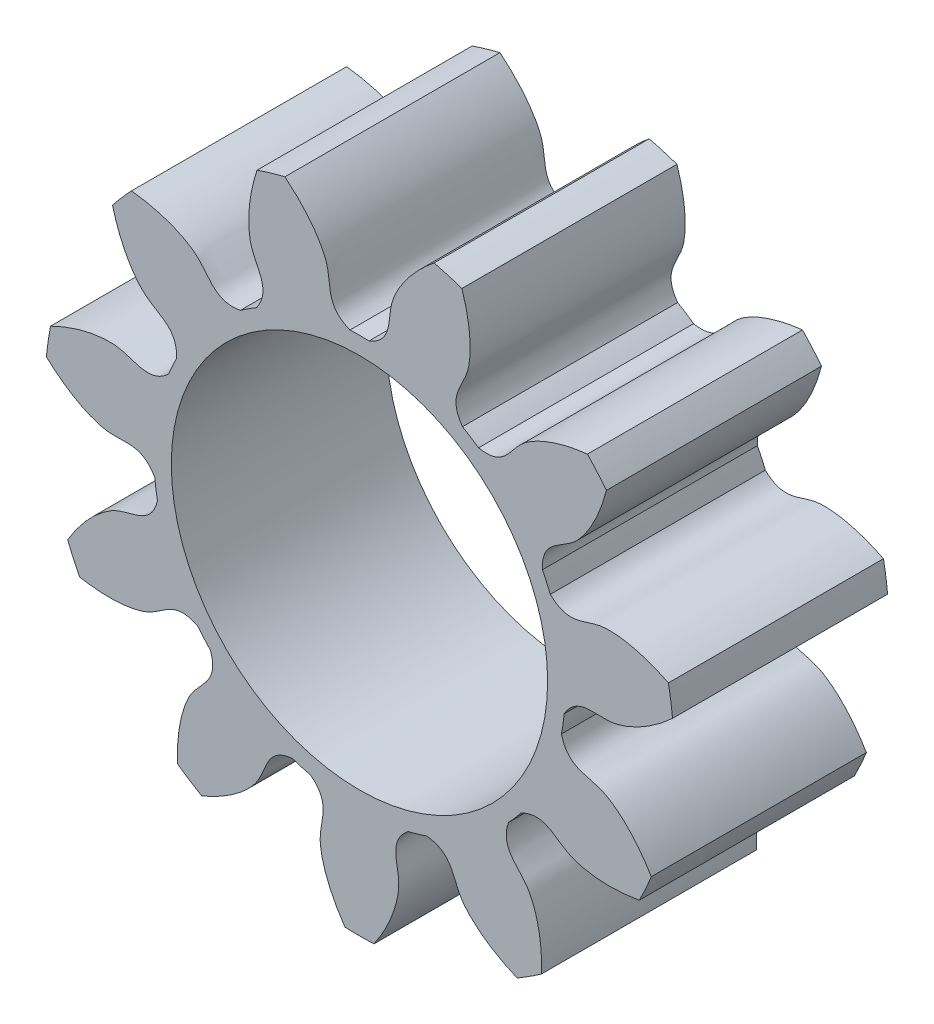
SolidWorks part; units mm, degrees
ref_plane "前视基准面" through (0, 0, 0) normal (0, 0, 1) x (1, 0, 0)
ref_plane "上视基准面" through (0, 0, 0) normal (0, 1, 0) x (1, 0, 0)
ref_plane "右视基准面" through (0, 0, 0) normal (1, 0, 0) x (0, 0, -1)
other "Configuration Table"
sketch "草图1" plane through (0, 0, 0) normal (0, 0, 1) x (1, 0, 0)
  circle A0 centre (0, 0) radius 2.925
extrude "凸台-拉伸1" add sketch "草图1" along normal blind 2
ref_axis "基准轴1" through (0, 0, 2) along (0, 0, -1)
sketch "草图2" plane through (0, 0, 0) normal (0, 0, 1) x (1, 0, 0)
  line L0 (0, 0) -> (0, 2.925) construction
  circle A0 centre (0, 0) radius 2.925 construction
  arc A1 (0.0885, 1.9104) -> (-0.0885, 1.9104) centre (0, 0) ccw
  arc A2 (1.6426, 3.2805) -> (-1.6426, 3.2805) centre (0, 0) ccw
  spline S0 degree 3 poles (0.0885, 1.9104) (0.3157, 2.001) (0.2586, 2.1861) (0.3071, 2.3434) (0.3099, 2.3518) (0.3131, 2.361) (0.3169, 2.371) (0.3212, 2.3818) (0.326, 2.3934) (0.3315, 2.4057) (0.3376, 2.4188) (0.3444, 2.4325) (0.3519, 2.447) (0.3602, 2.4621) (0.3692, 2.4779) (0.3789, 2.4942) (0.3895, 2.5112) (0.401, 2.5287) (0.4133, 2.5468) (0.4265, 2.5654) (0.4407, 2.5844) (0.4558, 2.6039) (0.4718, 2.6238) (0.4889, 2.6441) (0.5069, 2.6648) (0.526, 2.6858) (0.5462, 2.707) (0.5674, 2.7286) (0.5898, 2.7503) (0.6132, 2.7722) (0.6378, 2.7943) (0.6635, 2.8165) (0.6903, 2.8388) (0.7183, 2.8611) (0.7475, 2.8834) (0.7779, 2.9057) (0.8095, 2.9279) (0.8423, 2.9499) (0.8764, 2.9718) (0.9116, 2.9936) (0.9481, 3.015) (0.9858, 3.0363) (1.0247, 3.0571) (1.0649, 3.0777) (1.1063, 3.0978) (1.149, 3.1175) (1.1929, 3.1367) (1.238, 3.1554) (1.2844, 3.1735) (1.332, 3.191) (1.3808, 3.2078) (1.4308, 3.224) (1.482, 3.2394) (1.5525, 3.2591) (1.6063, 3.2723) (1.6426, 3.2805) knots 0 0 0 0 0.219011 0.222642 0.226699 0.231184 0.236096 0.241435 0.247201 0.253394 0.260015 0.267062 0.274537 0.282438 0.290767 0.299523 0.308706 0.318316 0.328354 0.338818 0.34971 0.361028 0.372774 0.384947 0.397547 0.410574 0.424029 0.43791 0.452219 0.466954 0.482117 0.497707 0.513724 0.530168 0.547039 0.564338 0.582063 0.600216 0.618795 0.637802 0.657236 0.677097 0.697385 0.718101 0.739243 0.760813 0.782809 0.805233 0.828084 0.851362 0.875067 0.8992 0.923759 0.948746 1 1 1 1
  spline S1 degree 3 poles (-0.0885, 1.9104) (-0.3157, 2.001) (-0.2586, 2.1861) (-0.3071, 2.3434) (-0.3099, 2.3518) (-0.3131, 2.361) (-0.3169, 2.371) (-0.3212, 2.3818) (-0.326, 2.3934) (-0.3315, 2.4057) (-0.3376, 2.4188) (-0.3444, 2.4325) (-0.3519, 2.447) (-0.3602, 2.4621) (-0.3692, 2.4779) (-0.3789, 2.4942) (-0.3895, 2.5112) (-0.401, 2.5287) (-0.4133, 2.5468) (-0.4265, 2.5654) (-0.4407, 2.5844) (-0.4558, 2.6039) (-0.4718, 2.6238) (-0.4889, 2.6441) (-0.5069, 2.6648) (-0.526, 2.6858) (-0.5462, 2.707) (-0.5674, 2.7286) (-0.5898, 2.7503) (-0.6132, 2.7722) (-0.6378, 2.7943) (-0.6635, 2.8165) (-0.6903, 2.8388) (-0.7183, 2.8611) (-0.7475, 2.8834) (-0.7779, 2.9057) (-0.8095, 2.9279) (-0.8423, 2.9499) (-0.8764, 2.9718) (-0.9116, 2.9936) (-0.9481, 3.015) (-0.9858, 3.0363) (-1.0247, 3.0571) (-1.0649, 3.0777) (-1.1063, 3.0978) (-1.149, 3.1175) (-1.1929, 3.1367) (-1.238, 3.1554) (-1.2844, 3.1735) (-1.332, 3.191) (-1.3808, 3.2078) (-1.4308, 3.224) (-1.482, 3.2394) (-1.5525, 3.2591) (-1.6063, 3.2723) (-1.6426, 3.2805) knots 0 0 0 0 0.219011 0.222642 0.226699 0.231184 0.236096 0.241435 0.247201 0.253394 0.260015 0.267062 0.274537 0.282438 0.290767 0.299523 0.308706 0.318316 0.328354 0.338818 0.34971 0.361028 0.372774 0.384947 0.397547 0.410574 0.424029 0.43791 0.452219 0.466954 0.482117 0.497707 0.513724 0.530168 0.547039 0.564338 0.582063 0.600216 0.618795 0.637802 0.657236 0.677097 0.697385 0.718101 0.739243 0.760813 0.782809 0.805233 0.828084 0.851362 0.875067 0.8992 0.923759 0.948746 1 1 1 1
extrude "切除-拉伸1" cut sketch "草图2" along normal through all
pattern_circular "阵列(圆周)1" count 11 every 32.727 about axis through (0, 0, 2) along (0, 0, -1) of "切除-拉伸1"
sketch "草图3" plane through (0, 0, 0) normal (0, 0, 1) x (1, 0, 0)
  circle A0 centre (0, 0) radius 2.475 construction
  dimension "Dn" = 4.95
sketch "草图4" plane through (0, 0, 2) normal (0, 0, 1) x (1, 0, 0)
  circle A0 centre (0, 0) radius 1.75
  dimension "D1" = 3.5
extrude "切除-拉伸2" cut sketch "草图4" against normal through all
